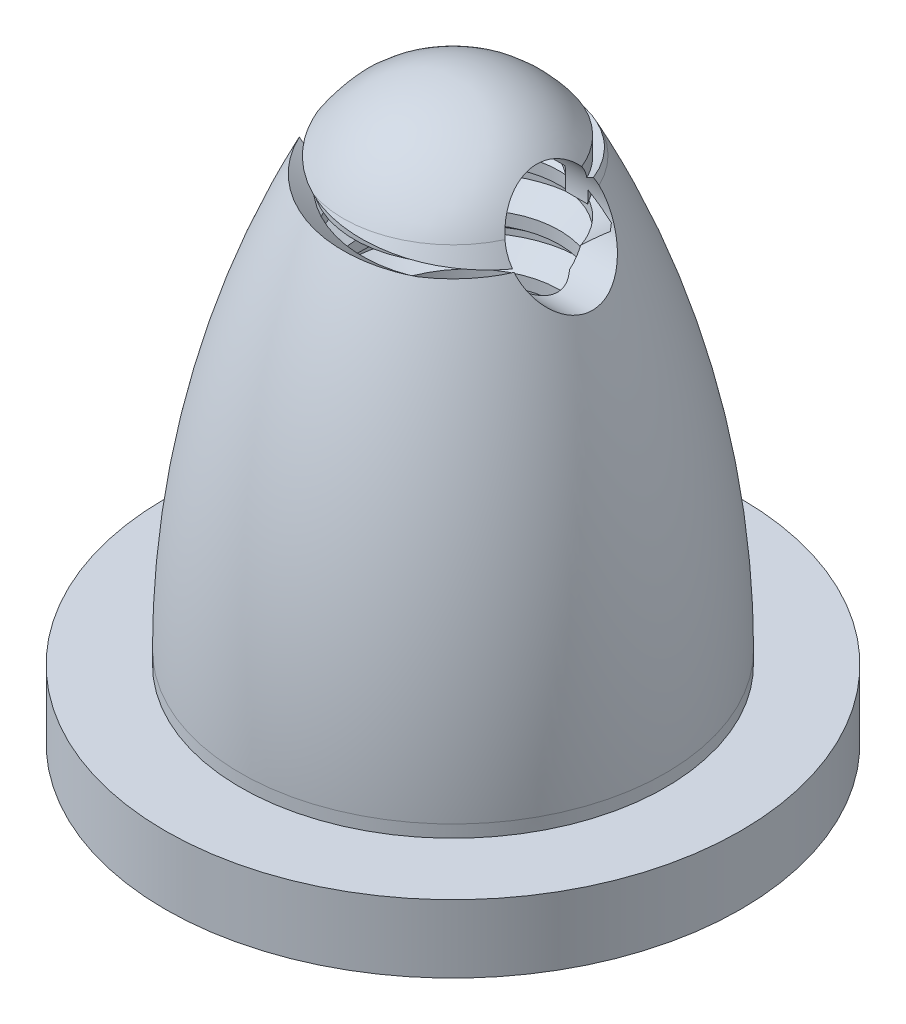
SolidWorks part; units mm, degrees
material "1060 Alloy"
ref_plane "Front" through (0, 0, 0) normal (0, 0, 1) x (1, 0, 0)
ref_plane "Top" through (0, 0, 0) normal (0, 1, 0) x (1, 0, 0)
ref_plane "Right" through (0, 0, 0) normal (1, 0, 0) x (0, 0, -1)
sketch "Sketch1" plane through (0, 0, 0) normal (0, 0, 1) x (1, 0, 0)
  line L0 (0, 11.8524) -> (-3.7832, 11.8524) construction
  line L1 (50, 0) -> (-50, 0) construction
  line L2 (5.9182, 0) -> (5.9182, 1.397)
  line L3 (5.9182, 1.397) -> (4.3708, 1.397)
  line L4 (4.3708, 1.397) -> (4.3708, 1.651)
  line L5 (0, -50) -> (0, 50) construction
  line L6 (0, 11.8524) -> (0, 10.4703)
  line L7 (0, 10.4703) -> (1.651, 10.4703)
  line L8 (1.651, 10.4703) -> (1.651, 9.9861)
  line L9 (1.651, 9.9861) -> (2.032, 9.9861)
  line L10 (2.032, 9.9861) -> (2.032, 0)
  line L11 (2.032, 0) -> (5.9182, 0)
  line L12 (3.683, 6.7756) -> (0, 6.7756) construction
  arc A0 (4.3708, 1.651) -> (2.2546, 10.4703) centre (-15.0655, 1.651) ccw
  arc A1 (2.2546, 10.4703) -> (0, 11.8524) centre (0, 9.3223) ccw
  dimension "D1" = 2.032
  dimension "D2" = 1.651
  dimension "D8" = 1.397
  dimension "D9" = 0.254
  dimension "D11" = 3.683
revolve "Revolve1" add sketch "Sketch1" angle 360 about L6
sketch "Sketch2" plane through (0, 0, 0) normal (1, 0, 0) x (0, 0, -1)
  line L2 (-5.9182, 0) -> (5.9182, 0) construction
  circle A0 centre (0, 10.16) radius 1.016
  dimension "D2" = 2.032
  dimension "D1" = 10.16
extrude "Cut-Extrude1" cut sketch "Sketch2" against normal through all both and the other way through all
sketch "Sketch3" plane through (0, 0, 0) normal (1, 0, 0) x (0, 0, -1)
  line L0 (-2.032, 0) -> (-2.032, -0.8043)
  line L1 (-2.032, -0.8043) -> (-2.4765, -0.4657)
  line L2 (-2.4765, -0.4657) -> (-2.4765, -0.3387)
  line L3 (-2.4765, -0.3387) -> (-2.032, 0)
  line L4 (-2.032, 0) -> (2.032, 0) construction
  dimension "D1" = 2.4765
  dimension "D2" = 0.127
  dimension "D3" = 0.8043
chamfer "Chamfer2" distance 0.508 angle 45 1 edges at (-2.032, 0, 0)
sketch "Sketch6" plane through (0, 0, 0) normal (0, -1, 0) x (1, 0, 0)
  circle A0 centre (0, 0) radius 2.032 construction
  circle A1 centre (0, 0) radius 2.032
curve "Helix/Spiral1" pitch 1.0583 height 11.43 turns 10.8
sweep "Cut-Sweep1" cut profiles "Sketch3" path "Helix/Spiral1" align with end faces yes
